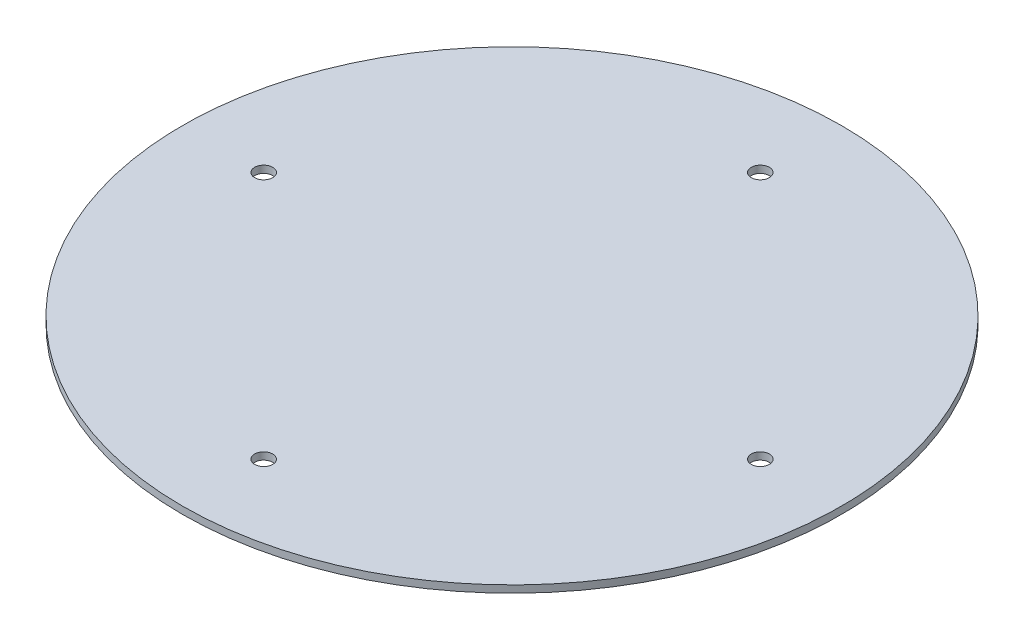
SolidWorks part; units mm, degrees
material "E-Glass Fiber"
ref_plane "Front Plane" through (0, 0, 0) normal (0, 0, 1) x (1, 0, 0)
ref_plane "Top Plane" through (0, 0, 0) normal (0, 1, 0) x (1, 0, 0)
ref_plane "Right Plane" through (0, 0, 0) normal (1, 0, 0) x (0, 0, -1)
sketch "Sketch1" plane through (0, 0, 0) normal (0, 1, 0) x (1, 0, 0)
  arc A0 (-65, -33.2265) -> (-33.2265, -65) centre (0, 0) ccw
  arc A1 (-65, 33.2265) -> (-65, -33.2265) centre (0, 0) ccw construction
  arc A2 (33.2265, 65) -> (-33.2265, 65) centre (0, 0) ccw construction
  arc A3 (-33.2265, 65) -> (-65, 33.2265) centre (0, 0) ccw
  arc A4 (65, -33.2265) -> (65, 33.2265) centre (0, 0) ccw construction
  arc A5 (65, 33.2265) -> (33.2265, 65) centre (0, 0) ccw
  arc A6 (-33.2265, -65) -> (33.2265, -65) centre (0, 0) ccw construction
  arc A7 (33.2265, -65) -> (65, -33.2265) centre (0, 0) ccw
  circle A8 centre (0, 0) radius 73
  point P14 (0, 0)
  dimension "D1" = 146
extrude "Boss-Extrude1" add sketch "Sketch1" along normal blind 1.6 contours A7 A8 A5 A3 A0 region at (0, 0, 0)
sketch "Sketch2" plane through (0, 1.6, 0) normal (0, 1, 0) x (1, 0, 0)
  line L0 (0, 0) -> (0, 55) construction
  line L3 (0, 0) -> (55, 0) construction
  line L4 (0, 0) -> (0, -55) construction
  line L6 (-55, 0) -> (0, 0) construction
  point P0 (0, 55)
  point P2 (55, 0)
  point P4 (-55, 0)
  point P6 (0, -55)
  dimension "D1" = 55
hole_wizard "Ø4.0mm Dowel Hole1" positions "Sketch2" profile "Sketch3" hole size "Ø4.0" standard "ISO" end condition through all
sketch "Sketch3" plane through (0, 1.6, -55) normal (1, 0, 0) x (0, 0, 1)
  line L0 (0, 0) -> (0, 1.6)
  line L1 (0, 1.6) -> (2, 1.6)
  line L2 (2, 1.6) -> (2, 0)
  line L5 (2, 0) -> (0, 0)
  line L11 (0, -6.35) -> (0, 107.95) construction
  dimension "Thru Hole Dia." = 4
  dimension "Thru Hole Depth" = 1.6
